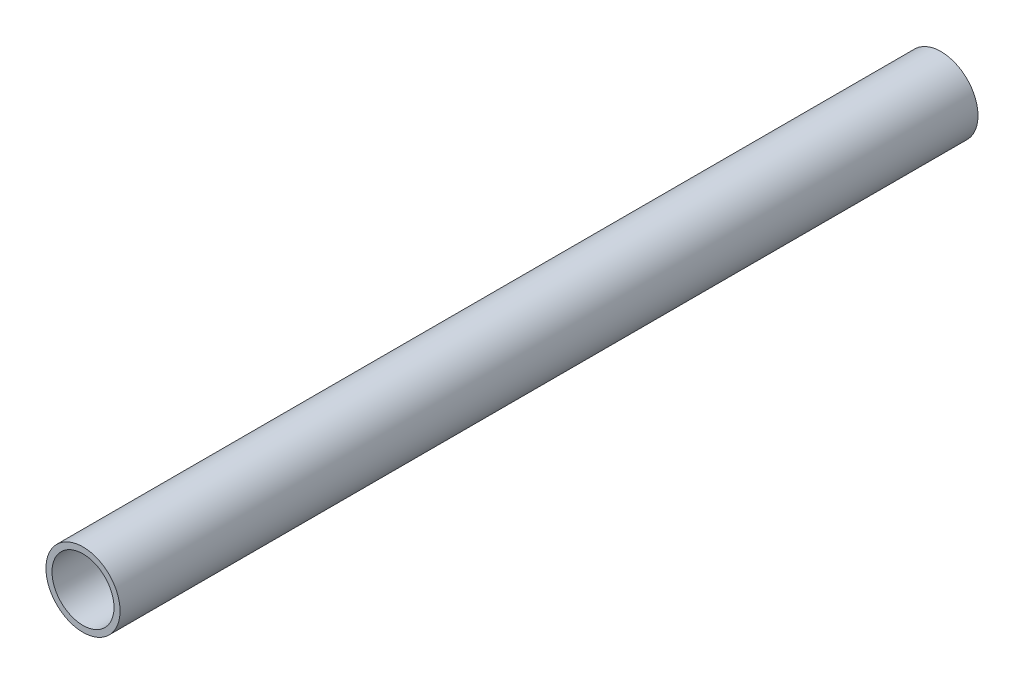
SolidWorks part; units mm, degrees
material "PVC Rigid"
ref_plane "Front Plane" through (0, 0, 0) normal (0, 0, 1) x (1, 0, 0)
ref_plane "Top Plane" through (0, 0, 0) normal (0, 1, 0) x (1, 0, 0)
ref_plane "Right Plane" through (0, 0, 0) normal (1, 0, 0) x (0, 0, -1)
sketch "Sketch1" plane through (0, 0, 0) normal (0, 0, 1) x (1, 0, 0)
  circle A0 centre (0, 0) radius 20.193
  circle A1 centre (0, 0) radius 24.13
  dimension "D1" = 48.26
  dimension "D2" = 40.386
extrude "Boss-Extrude1" add sketch "Sketch1" along normal blind 558.8
ref_axis "Axis1" through (0, 0, 586.8837) along (0, 0, -1)
